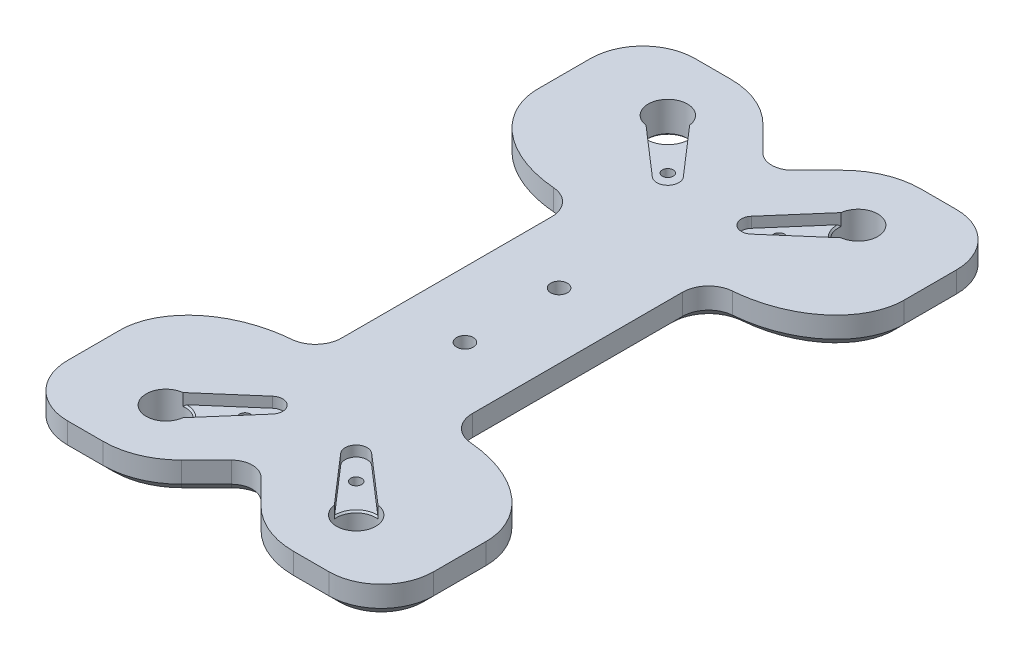
SolidWorks part; units mm, degrees
ref_plane "Plan de face" through (0, 0, 0) normal (0, 0, 1) x (1, 0, 0)
ref_plane "Plan de dessus" through (0, 0, 0) normal (0, 1, 0) x (1, 0, 0)
ref_plane "Plan de droite" through (0, 0, 0) normal (1, 0, 0) x (0, 0, -1)
sketch "Esquisse2" plane through (0, 0, 0) normal (0, 1, 0) x (1, 0, 0)
  line L0 (0, -60) -> (0, 60) construction
  line L1 (0, 0) -> (-68.0838, 0) construction
  line L2 (-12.5, -25) -> (-12.5, 25)
  line L3 (-12.5, 25) -> (-35, 25)
  line L4 (-35, 25) -> (-35, 60)
  line L5 (-35, 60) -> (35, 60)
  line L6 (12.5, -25) -> (12.5, 25)
  line L7 (35, 25) -> (35, 60)
  line L8 (12.5, 25) -> (35, 25)
  line L9 (12.5, -25) -> (35, -25)
  line L10 (35, -25) -> (35, -60)
  line L11 (-35, -60) -> (35, -60)
  line L12 (-35, -25) -> (-35, -60)
  line L13 (-12.5, -25) -> (-35, -25)
  circle A0 centre (-18.2, 48) radius 3.75
  circle A1 centre (18.2, 48) radius 3.75
  circle A2 centre (18.2, -48) radius 3.75
  circle A3 centre (-18.2, -48) radius 3.75
  circle A4 centre (0, 9) radius 1.6
  circle A5 centre (0, -9) radius 1.6
  point P24 (12.5, 0)
  point P27 (-12.5, 0)
  dimension "D5" = 7.5
  dimension "D8" = 3.2
  dimension "D9" = 3.2
  dimension "D10" = 9
  dimension "D11" = 9
  dimension "D1" = 60
  dimension "D2" = 35
  dimension "D3" = 35
  dimension "D4" = 12.5
  dimension "D6" = 16.8
  dimension "D7" = 12
extrude "Boss.-Extru.1" add sketch "Esquisse2" along normal blind 6
fillet "Congé1" radius 10 4 edges at (-35, 3, -60) (35, 3, -60) (-35, 3, 60) (35, 3, 60)
fillet "Congé2" radius 15 2 edges at (35, 3, 25) (-35, 3, -25)
fillet "Congé3" radius 15 2 edges at (-35, 3, 25) (35, 3, -25)
fillet "Congé4" radius 5 4 edges at (-12.5, 3, 25) (-12.5, 3, -25) (12.5, 3, -25) (12.5, 3, 25)
sketch "Esquisse3" plane through (0, 6, 0) normal (0, 1, 0) x (1, 0, 0)
  line L0 (-18.2, 48) -> (-4.6259, 34.4259) construction
  line L1 (-18.6489, 44.277) -> (-14.477, 48.4489) construction
  line L2 (-18.6489, 44.277) -> (-9.4652, 36.3027)
  line L3 (-14.477, 48.4489) -> (-6.5027, 39.2652)
  line L4 (25, 60) -> (-25, 60) construction
  line L5 (0, 60) -> (0, -60) construction
  line L6 (-25, -60) -> (25, -60) construction
  line L7 (18.6489, 44.277) -> (14.477, 48.4489) construction
  line L8 (18.2, 48) -> (4.6259, 34.4259) construction
  line L9 (14.477, 48.4489) -> (6.5027, 39.2652)
  line L10 (18.6489, 44.277) -> (9.4652, 36.3027)
  line L11 (-12.5, 0) -> (12.5, 0) construction
  line L12 (-12.5, 20.0989) -> (-12.5, -20.0989) construction
  line L13 (12.5, -20.0989) -> (12.5, 20.0989) construction
  line L14 (18.2, -48) -> (4.6259, -34.4259) construction
  line L15 (18.6489, -44.277) -> (14.477, -48.4489) construction
  line L16 (-18.6489, -44.277) -> (-14.477, -48.4489) construction
  line L17 (-18.2, -48) -> (-4.6259, -34.4259) construction
  line L18 (18.6489, -44.277) -> (9.4652, -36.3027)
  line L19 (14.477, -48.4489) -> (6.5027, -39.2652)
  line L20 (-14.477, -48.4489) -> (-6.5027, -39.2652)
  line L21 (-18.6489, -44.277) -> (-9.4652, -36.3027)
  circle A0 centre (-18.2, 48) radius 3.75
  arc A1 (-9.4652, 36.3027) -> (-6.5027, 39.2652) centre (-8.0884, 37.8884) ccw
  circle A2 centre (-18.2, 48) radius 3.75 construction
  arc A3 (9.4652, 36.3027) -> (6.5027, 39.2652) centre (8.0884, 37.8884) cw
  circle A4 centre (18.2, 48) radius 3.75
  circle A5 centre (18.2, -48) radius 3.75
  arc A6 (9.4652, -36.3027) -> (6.5027, -39.2652) centre (8.0884, -37.8884) ccw
  arc A7 (-9.4652, -36.3027) -> (-6.5027, -39.2652) centre (-8.0884, -37.8884) cw
  circle A8 centre (-18.2, -48) radius 3.75
  point P2 (-8.0884, 37.8884)
  point P25 (8.0884, 37.8884)
  point P48 (8.0884, -37.8884)
  point P49 (-8.0884, -37.8884)
  dimension "D1" = 7.5
  dimension "D4" = 2.1
  dimension "D2" = 14.3
  dimension "D3" = 5.9
  dimension "D5" = 45
extrude "Enlèv. mat.-Extru.1" cut sketch "Esquisse3" against normal blind 2 contours L2 A1 L3 A0 | L10 A4 L9 A3 | L18 A6 L19 A5 | L21 A8 L20 A7
sketch "Esquisse4" plane through (0, 4, 0) normal (0, 1, 0) x (1, 0, 0)
  line L0 (-15.5483, 45.3483) -> (-6.6034, 36.4034) construction
  line L1 (0, 7.2535) -> (0, -10.7762) construction
  line L2 (-6.6034, 0) -> (8.3729, 0) construction
  line L3 (15.5483, 45.3483) -> (6.6034, 36.4034) construction
  line L4 (15.5483, -45.3483) -> (6.6034, -36.4034) construction
  line L5 (-15.5483, -45.3483) -> (-6.6034, -36.4034) construction
  arc A0 (-18.6489, 44.277) -> (-14.477, 48.4489) centre (-18.2, 48) ccw construction
  arc A1 (-9.4652, 36.3027) -> (-6.5027, 39.2652) centre (-8.0884, 37.8884) ccw construction
  circle A2 centre (-10.634, 40.434) radius 1.05
  arc A3 (-14.477, 48.4489) -> (-18.6489, 44.277) centre (-18.2, 48) ccw construction
  circle A4 centre (10.634, 40.434) radius 1.05
  circle A5 centre (10.634, -40.434) radius 1.05
  circle A6 centre (-10.634, -40.434) radius 1.05
  dimension "D1" = 2.1
  dimension "D2" = 10.7
extrude "Enlèv. mat.-Extru.2" cut sketch "Esquisse4" against normal up to next
chamfer "Chanfrein2" distance 0.3 angle 45 10 edges at (-15.5483, 4, -45.3483) (15.5483, 4, -45.3483) (15.5483, 4, 45.3483) (-15.5483, 4, 45.3483) (18.2, 0, -51.75) (-18.2, 0, -44.25) (-10.634, 0, -41.484) (10.634, 0, -41.484) (10.634, 0, 39.384) (-10.634, 0, 39.384)
chamfer "Chanfrein3" distance 1.8 angle 45 2 edges at (0, 0, 10.6) (0, 0, -7.4)
sketch "Esquisse5" plane through (0, 6, 0) normal (0, 1, 0) x (1, 0, 0)
  line L0 (-12, -60) -> (0, -48)
  line L1 (-25, -60) -> (25, -60) construction
  line L2 (0, -48) -> (12, -60)
  line L3 (-35, -40) -> (-35, -50) construction
  line L4 (35, -50) -> (35, -40) construction
  line L5 (-12, -60) -> (12, -60)
  line L6 (-22.1765, 0) -> (20.7464, 0) construction
  line L7 (-12, 60) -> (12, 60)
  line L8 (0, 48) -> (12, 60)
  line L9 (-12, 60) -> (0, 48)
  dimension "D1" = 45
  dimension "D2" = 45
  dimension "D3" = 23
  dimension "D4" = 23
extrude "Enlèv. mat.-Extru.3" cut sketch "Esquisse5" against normal blind 10
fillet "Congé5" radius 15 4 edges at (-12, 3, 60) (12, 3, 60) (-12, 3, -60) (12, 3, -60)
fillet "Congé6" radius 4 2 edges at (0, 3, -48) (0, 3, 48)
chamfer "Chanfrein4" distance 2 angle 45 32 edges at (12.5, 0, 0) (32.0711, 0, -57.0711) (32.0711, 0, 57.0711) (21.6066, 0, -60) (21.6066, 0, 60) (12.473, 0, -58.8582) (12.473, 0, 58.8582) (5.2175, 0, -53.2175) (5.2175, 0, 53.2175) (0, 0, -49.6569) (0, 0, 49.6569) (-5.2175, 0, -53.2175) (-5.2175, 0, 53.2175) (-12.473, 0, -58.8582) (-12.473, 0, 58.8582) (-21.6066, 0, -60) (-21.6066, 0, 60) (-32.0711, 0, -57.0711) (-32.0711, 0, 57.0711) (-12.5, 0, 0)
